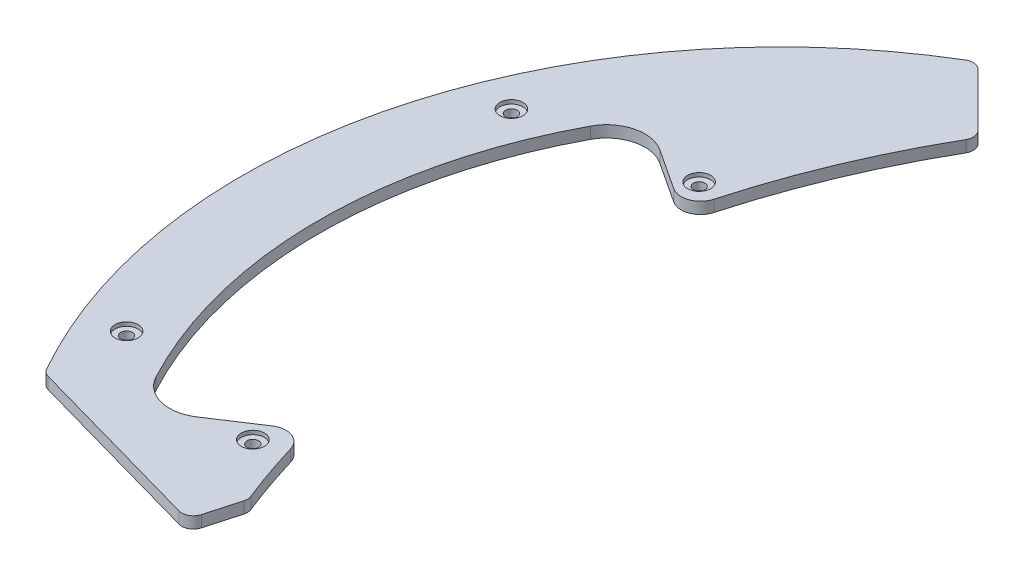
SolidWorks part; units mm, degrees
material "1060 Alloy"
ref_plane "Front Plane" through (0, 0, 0) normal (0, 0, 1) x (1, 0, 0)
ref_plane "Top Plane" through (0, 0, 0) normal (0, 1, 0) x (1, 0, 0)
ref_plane "Right Plane" through (0, 0, 0) normal (1, 0, 0) x (0, 0, -1)
sketch "Sketch1" plane through (0, 0, 0) normal (0, 1, 0) x (1, 0, 0)
  circle A0 centre (0, 0) radius 140
  dimension "D1" = 280
extrude "Boss-Extrude1" add sketch "Sketch1" along normal blind 3
sketch "Sketch17" plane through (0, 0, 0) normal (0, -1, 0) x (1, 0, 0)
  line L0 (-50, 90) -> (-121.2436, 70)
  line L1 (-50, 90) -> (50, 90)
  line L2 (-121.2436, 70) -> (-121.2436, 140)
  line L3 (-121.2436, 140) -> (121.2436, 140)
  line L4 (121.2436, 140) -> (121.2436, 70)
  line L5 (121.2436, 70) -> (50, 90)
  circle A0 centre (0, 0) radius 140 construction
  dimension "D1" = 90
  dimension "D2" = 50
  dimension "D3" = 50
  dimension "D4" = 70
extrude "Cut-Extrude1" cut sketch "Sketch17" against normal up to next
sketch "Sketch19" plane through (0, 3, 0) normal (0, 1, 0) x (1, 0, 0)
  line L0 (-68.5894, 68.5894) -> (68.5894, -68.5894) construction
  line L1 (97, 40.1787) -> (40.1787, 97) construction
  line L2 (40.1787, 97) -> (-40.1787, 97) construction
  line L3 (-40.1787, 97) -> (-97, 40.1787) construction
  line L4 (-97, 40.1787) -> (-97, -40.1787) construction
  line L5 (-97, -40.1787) -> (-40.1787, -97) construction
  line L6 (-40.1787, -97) -> (40.1787, -97) construction
  line L7 (40.1787, -97) -> (97, -40.1787) construction
  line L8 (97, -40.1787) -> (97, 40.1787) construction
  line L9 (68.5894, 68.5894) -> (-68.5894, -68.5894) construction
  circle A0 centre (-79.196, -57.9828) radius 1.5
  circle A1 centre (-79.196, 57.9828) radius 1.5
  circle A2 centre (79.196, 57.9828) radius 1.5
  circle A3 centre (79.196, -57.9828) radius 1.5
  circle A4 centre (0, 0) radius 97 construction
  circle A5 centre (-57.9828, 79.196) radius 1.5
  circle A6 centre (57.9828, 79.196) radius 1.5
  circle A7 centre (57.9828, -79.196) radius 1.5
  circle A8 centre (-57.9828, -79.196) radius 1.5
  dimension "D5" = 3
  dimension "D1" = 15
  dimension "D6" = 97
extrude "Cut-Extrude3" cut sketch "Sketch19" against normal up to next
sketch "Sketch20" plane through (0, 3, 0) normal (0, 1, 0) x (1, 0, 0)
  line L0 (-70, 121.2436) -> (-50, 101.2436)
  line L1 (-50, 101.2436) -> (50, 101.2436)
  line L2 (50, 101.2436) -> (70, 121.2436)
  arc A1 (121.2436, -70) -> (-121.2436, -70) centre (0, 0) ccw construction
  dimension "D1" = 140
  dimension "D2" = 100
  dimension "D3" = 50
extrude "Cut-Extrude4" cut sketch "Sketch20" against normal up to next
sketch "Sketch21" plane through (0, 3, 0) normal (0, 1, 0) x (1, 0, 0)
  line L0 (-52.1633, 87.3282) -> (0, 50)
  line L1 (0, 50) -> (52.1633, 87.3282)
  line L2 (66.2648, 73.5916) -> (30, 20)
  line L3 (30, 20) -> (67.2983, -75.56)
  line L4 (49.6537, -84.7301) -> (0, -10) construction
  line L5 (0, -10) -> (-49.6537, -84.7301) construction
  line L6 (-67.2983, -75.56) -> (-30, 20)
  line L7 (-30, 20) -> (-66.2648, 73.5916)
  line L8 (-67.2983, -75.56) -> (-72.9344, -90)
  line L9 (-72.9344, -90) -> (72.9344, -90)
  line L10 (72.9344, -90) -> (67.2983, -75.56)
  line L11 (-50, -90) -> (50, -90) construction
  line L12 (-68.5894, 68.5894) -> (68.5894, -68.5894) construction
  line L13 (97, 40.1787) -> (40.1787, 97) construction
  line L14 (40.1787, 97) -> (-40.1787, 97) construction
  line L15 (-40.1787, 97) -> (-97, 40.1787) construction
  line L16 (-97, 40.1787) -> (-97, -40.1787) construction
  line L17 (-97, -40.1787) -> (-40.1787, -97) construction
  line L18 (-40.1787, -97) -> (40.1787, -97) construction
  line L19 (40.1787, -97) -> (97, -40.1787) construction
  line L20 (97, -40.1787) -> (97, 40.1787) construction
  line L21 (68.5894, 68.5894) -> (-68.5894, -68.5894) construction
  arc A0 (-66.2648, 73.5916) -> (-52.1633, 87.3282) centre (-57.9828, 79.196) cw
  arc A1 (66.2648, 73.5916) -> (52.1633, 87.3282) centre (57.9828, 79.196) ccw
  arc A2 (-49.6537, -84.7301) -> (-67.2983, -75.56) centre (-57.9828, -79.196) cw construction
  arc A3 (67.2983, -75.56) -> (49.6537, -84.7301) centre (57.9828, -79.196) cw construction
  circle A5 centre (0, 0) radius 97 construction
  dimension "D2" = 10
  dimension "D3" = 15
  dimension "D8" = 97
extrude "Cut-Extrude5" [suppressed] cut sketch "Sketch21" against normal up to next
fillet "Fillet1" [suppressed] radius 20
fillet "Fillet2" radius 10 2 edges at (50, 1.5, -101.2436) (-50, 1.5, -101.2436)
sketch "Sketch22" plane through (0, 3, 0) normal (0, 1, 0) x (1, 0, 0)
  line L1 (85, 24) -> (118, 24)
  line L2 (85, 24) -> (85, -24)
  line L3 (85, -24) -> (118, -24)
  line L4 (118, 24) -> (118, -24)
  line L5 (-118, 26) -> (-85, 26)
  line L6 (-118, 26) -> (-118, -27)
  line L7 (-118, -27) -> (-85, -27)
  line L8 (-85, 26) -> (-85, -27)
  dimension "D1" = 85
  dimension "D2" = 85
  dimension "D3" = 48
  dimension "D4" = 53
  dimension "D5" = 33
  dimension "D6" = 33
  dimension "D7" = 26
  dimension "D8" = 24
extrude "Cut-Extrude6" [suppressed] cut sketch "Sketch22" against normal up to next
fillet "Fillet3" [suppressed] radius 3
sketch "Sketch23" plane through (0, 3, 0) normal (0, 1, 0) x (1, 0, 0)
  line L0 (-66.3365, -71.9548) -> (-73.1897, -96.3671)
  line L1 (-70, 121.2436) -> (-52.9289, 104.1725) construction
  line L2 (-121.2436, -70) -> (-50, -90) construction
  arc A0 (-52.9289, 104.1725) -> (-66.3365, -71.9548) centre (119.2928, 2.4883) ccw
  arc A3 (-66.3365, -71.9548) -> (-52.9289, -99.196) centre (119.2928, 2.4883) ccw construction
  circle A4 centre (-57.9828, -79.196) radius 1.5 construction
  dimension "D2" = 20
  dimension "D3" = 200
  dimension "D4" = 90
  dimension "D5" = 10
extrude "Cut-Extrude8" cut sketch "Sketch23" against normal through all and the other way through all
sketch "Sketch24" plane through (0, 3, 0) normal (0, 1, 0) x (1, 0, 0)
  line L0 (0, 0) -> (-100.309, 65.8643)
  line L1 (-100.309, -65.8643) -> (0, 0)
  arc A0 (-100.309, 65.8643) -> (-100.309, -65.8643) centre (0, 0) ccw
  circle A1 centre (-79.196, 57.9828) radius 1.5 construction
  circle A2 centre (-79.196, -57.9828) radius 1.5 construction
  arc A3 (-70, 121.2436) -> (-121.2436, -70) centre (0, 0) ccw construction
  dimension "D2" = 5
  dimension "D3" = 20
  dimension "D1" = 5
extrude "Cut-Extrude9" cut sketch "Sketch24" against normal up to next
fillet "Fillet4" radius 5 2 edges at (-74.0638, 1.5, 48.6314) (-75.1422, 1.5, -49.3395)
fillet "Fillet6" radius 10 2 edges at (-100.309, 1.5, -65.8643) (-100.309, 1.5, 65.8643)
sketch "Sketch25" plane through (0, 3, 0) normal (0, 1, 0) x (1, 0, 0)
  circle A0 centre (-120, 50) radius 1.5
  circle A1 centre (-120, -50) radius 1.5
  dimension "D1" = 3
  dimension "D2" = 50
  dimension "D3" = 50
  dimension "D4" = 120
extrude "Cut-Extrude10" cut sketch "Sketch25" against normal up to next
fillet "Fillet5" radius 3 5 edges at (-70, 1.5, -121.2436) (-66.3365, 1.5, 71.9548) (-69.8389, 1.5, 84.4307) (-121.2436, 1.5, 70) (-52.9289, 1.5, -104.1725)
sketch "Sketch26" plane through (0, 3, 0) normal (0, 1, 0) x (1, 0, 0)
  circle A0 centre (-79.196, 57.9828) radius 3
  circle A1 centre (-120, 50) radius 3
  circle A2 centre (-120, -50) radius 3
  circle A3 centre (-79.196, -57.9828) radius 3
  dimension "D1" = 6
extrude "Cut-Extrude11" cut sketch "Sketch26" against normal blind 1
equation "\"D3@Sketch20\" = \"D2@Sketch20\" / 2"
